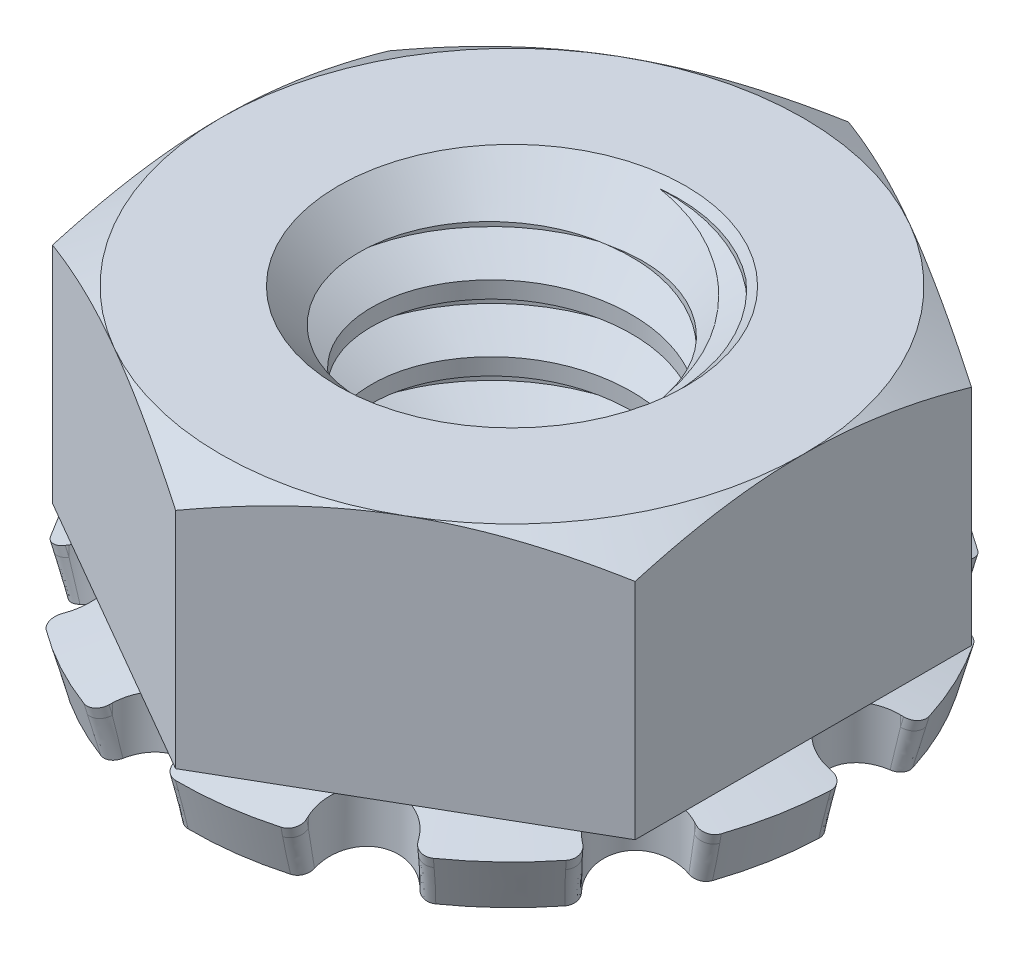
SolidWorks part; units mm, degrees
ref_plane "Front Plane" through (0, 0, 0) normal (0, 0, 1) x (1, 0, 0)
ref_plane "Top Plane" through (0, 0, 0) normal (0, 1, 0) x (1, 0, 0)
ref_plane "Right Plane" through (0, 0, 0) normal (1, 0, 0) x (0, 0, -1)
sketch "Sketch1" plane through (0, 0, 0) normal (0, 1, 0) x (1, 0, 0)
  line L1 (0, 6.4158) -> (-5.5562, 3.2079)
  line L2 (-5.5562, 3.2079) -> (-5.5562, -3.2079)
  line L3 (-5.5562, -3.2079) -> (0, -6.4158)
  line L4 (0, -6.4158) -> (5.5563, -3.2079)
  line L5 (5.5563, -3.2079) -> (5.5562, 3.2079)
  line L6 (5.5562, 3.2079) -> (0, 6.4158)
  circle A0 centre (0, 0) radius 5.5562 construction
  circle A1 centre (0, 0) radius 6.35 construction
  point P9 (0, 6.4158)
  point P10 (0, 6.35)
  dimension "Wd." = 11.1125
  dimension "Washer Dia." = 12.7
extrude "Boss-Extrude1" add sketch "Sketch1" along normal blind 5.9531
sketch "Sketch4" plane through (0, 5.9531, 0) normal (0, 1, 0) x (1, 0, 0)
  circle A0 centre (0, 0) radius 3.175
  dimension "Screw Dia." = 6.35
sketch "Sketch5" plane through (0, 5.9531, 0) normal (0, 1, 0) x (1, 0, 0)
  circle A1 centre (0, 0) radius 3.175
  circle A2 centre (0, 0) radius 3.175
  point P0 (0, 3.175)
  dimension "D1" = 0
curve "Helix/Spiral1" pitch 1.27 height 7.2231 turns 5.6875 parameters "Pitch"=1.27
sketch "Sketch2" plane through (0, 5.9531, 0) normal (0, 1, 0) x (1, 0, 0)
  circle A0 centre (0, 0) radius 5.5562 construction
  circle A1 centre (0, 0) radius 5.5562
  point P3 (0, 5.5562)
extrude "Cut-Extrude1" cut sketch "Sketch2" against normal through all draft 60 flip side to cut
sketch "Sketch3" plane through (0, 0, 0) normal (0, -1, 0) x (1, 0, 0)
  circle A1 centre (0, 0) radius 5.5562
  circle A2 centre (0, 0) radius 5.5562
  dimension "D1" = 0
extrude "Cut-Extrude2" [suppressed] cut sketch "Sketch3" against normal through all draft 60 flip side to cut
extrude "Cut-Extrude3" cut sketch "Sketch4" against normal up to vertex (5.9531 mm away) up to point (0, 0, 0)
sketch "Sketch6" plane through (0, 0, 0) normal (1, 0, 0) x (0, 0, -1)
  line L0 (3.3125, 7.1437) -> (3.3125, 5.8737) construction
  line L1 (3.3125, 5.8737) -> (2.2126, 6.5088) construction
  line L2 (2.2126, 6.5088) -> (3.3125, 7.1437) construction
  line L3 (2.3501, 6.5881) -> (2.3501, 6.4294) construction
  line L4 (2.2126, 6.5088) -> (2.3501, 6.5088) construction
  line L5 (3.175, 7.0644) -> (3.175, 5.9531) construction
  line L6 (3.175, 6.5088) -> (3.3125, 6.5088) construction
  line L7 (3.2437, 7.1041) -> (2.4876, 6.6675)
  line L8 (2.4876, 6.6675) -> (2.4876, 6.35)
  line L9 (2.4876, 6.35) -> (3.2437, 5.9134)
  line L10 (3.2437, 5.9134) -> (3.2437, 7.1041)
  line L11 (2.3501, 6.5088) -> (2.4876, 6.5088) construction
  point P13 (3.2437, 6.5088)
  dimension "D1" = 1.27
  dimension "D2" = 0.1588
sweep "Sweep1" add profiles "Sketch6" path "Helix/Spiral1"
sketch "Sketch7" plane through (0, 5.9531, 0) normal (0, 1, 0) x (1, 0, 0)
  line L0 (-3.3125, 0) -> (0, 0) construction
  circle A0 centre (0, 0) radius 3.3125
extrude "Cut-Extrude4" cut sketch "Sketch7" against normal through all draft 45 and the other way through all draft 45
sketch "Sketch8" plane through (0, 0, 0) normal (0, -1, 0) x (1, 0, 0)
  circle A1 centre (0, 0) radius 3.3125
  circle A2 centre (0, 0) radius 3.3125
  dimension "D1" = 0
extrude "Cut-Extrude5" cut sketch "Sketch8" against normal through all draft 45 and the other way through all draft 45
sketch "Sketch9" plane through (0, 0, 0) normal (1, 0, 0) x (0, 0, -1)
  line L0 (6.35, 0) -> (-6.35, 0) construction
  line L1 (4.3656, 0) -> (6.4158, 0)
  line L2 (0, 0) -> (0, 1.1906) construction
  line L3 (4.3656, 1.1906) -> (6.4158, 1.1906)
  line L4 (6.4158, 0) -> (6.4158, 1.1906)
  line L5 (0, 1.1906) -> (0, 5.9531) construction
  line L6 (4.3656, 1.1906) -> (4.3656, 0)
  line L7 (3.175, 5.9531) -> (3.175, 1.1906) construction
  line L8 (3.175, 1.1906) -> (4.3656, 1.1906) construction
  dimension "D" = 4.7625
revolve "Cut-Revolve1" cut sketch "Sketch9" angle 360 mid plane about L2
sketch "Sketch10" plane through (0, 0, 0) normal (1, 0, 0) x (0, 0, -1)
  line L0 (4.3656, 1.1906) -> (4.3656, 0) construction
  line L1 (4.3656, 1.1906) -> (5.375, 1.1906)
  line L2 (4.3656, 1.1906) -> (4.3656, 0.2612)
  line L3 (4.3656, 0.2612) -> (5.126, 0.2612)
  line L4 (6.35, 0.9294) -> (6.101, 0)
  line L5 (0, 1.1906) -> (0, 0) construction
  line L6 (6.35, 0.9294) -> (5.375, 1.1906)
  line L7 (6.101, 0) -> (5.126, 0.2612)
  line L8 (5.126, 0.2612) -> (5.375, 1.1906) construction
  line L9 (4.3656, 0) -> (6.4158, 0) construction
  dimension "D1" = 165
revolve "Revolve1" add sketch "Sketch10" angle 360 mid plane about L5
sketch "Sketch11" plane through (0, 0, 0) normal (0, 1, 0) x (1, 0, 0)
  line L0 (0, 0) -> (6.35, 0) construction
  line L1 (0, 0) -> (6.1336, 1.6435) construction
  line L2 (5.8427, 1.5655) -> (6.1336, 1.6435)
  line L3 (6.0488, 0) -> (6.35, 0)
  circle A0 centre (0, 0) radius 6.35 construction
  arc A1 (5.8427, 1.5655) -> (6.0488, 0) centre (6.0488, 0.7963) ccw
  arc A2 (6.35, 0) -> (6.1336, 1.6435) centre (0, 0) ccw
  circle A3 centre (0, 0) radius 6.101 construction
  dimension "D1" = 15
extrude "Cut-Extrude6" cut sketch "Sketch11" along normal up to vertex (1.1906 mm away) up to point (0, 1.1906, 0)
fillet "Fillet1" radius 0.254 2 edges at (6.0134, 0.4647, -1.6113) (6.2255, 0.4647, 0)
pattern_circular "CirPattern1" count 10 over 360 about axis through (0, 0, 0) along (0, -1, 0) of "Cut-Extrude6", "Fillet1"
equation "\"D3@Helix/Spiral1\" = \"Pitch@Helix/Spiral1\" + \"Ht.@Boss-Extrude1\""
equation "\"D1@Sketch6\" = \"Pitch@Helix/Spiral1\""
equation "\"D2@Sketch6\" = \"D1@Sketch6\" / 8"
